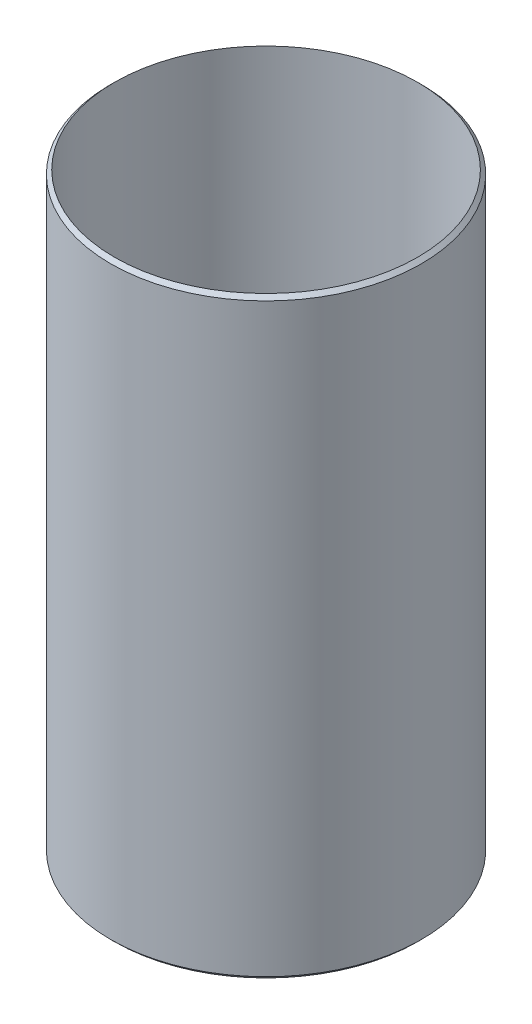
SolidWorks part; units mm, degrees
material "6061-T6 (SS)"
ref_plane "Front Plane" through (0, 0, 0) normal (0, 0, 1) x (1, 0, 0)
ref_plane "Top Plane" through (0, 0, 0) normal (0, 1, 0) x (1, 0, 0)
ref_plane "Right Plane" through (0, 0, 0) normal (1, 0, 0) x (0, 0, -1)
sketch "Sketch1" plane through (0, 0, 0) normal (0, 1, 0) x (1, 0, 0)
  circle A0 centre (0, 0) radius 80.55
  circle A1 centre (0, 0) radius 82.55
  dimension "D1" = 165.1
  dimension "D2" = 2
extrude "Boss-Extrude1" add sketch "Sketch1" along normal blind 315
chamfer "Chamfer1" distance 2 angle 45 2 edges at (0, 0, 82.55) (0, 315, 82.55)
equation "\"TubeDiameter\" = 6.500in"
equation "\"D1@Sketch1\"=\"TubeDiameter\""
